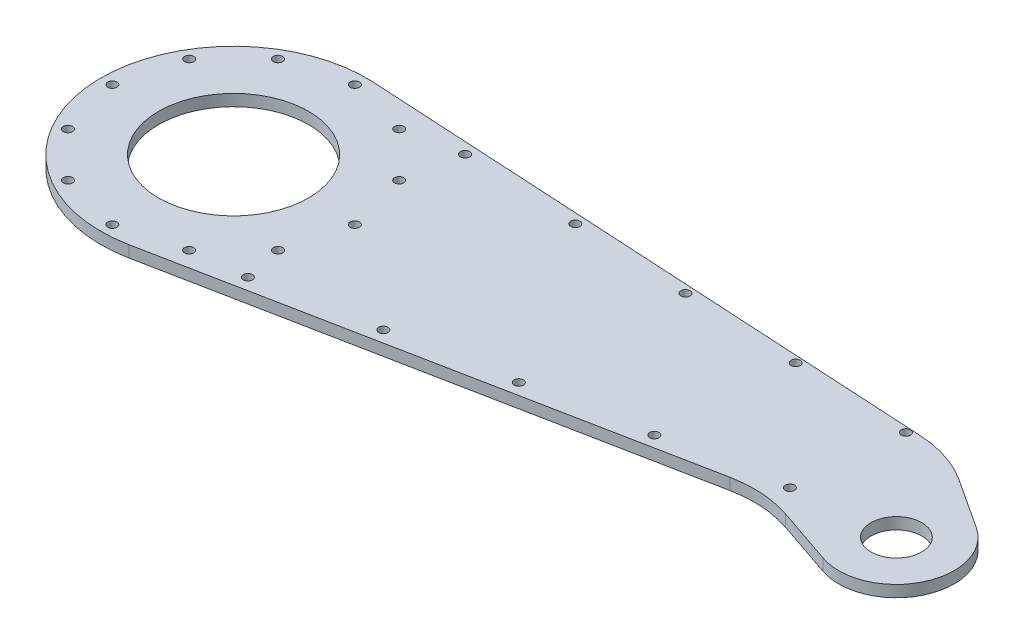
SolidWorks part; units mm, degrees
ref_plane "Front Plane" through (0, 0, 0) normal (0, 0, 1) x (1, 0, 0)
ref_plane "Top Plane" through (0, 0, 0) normal (0, 1, 0) x (1, 0, 0)
ref_plane "Right Plane" through (0, 0, 0) normal (1, 0, 0) x (0, 0, -1)
sketch "Sketch1" plane through (0, 0, 0) normal (0, 1, 0) x (1, 0, 0)
  line L0 (0, 0) -> (287, 0) construction
  line L1 (0, 0) -> (0, 57.5) construction
  line L2 (3.2274, 57.4094) -> (11.1373, -56.4111) construction
  line L3 (300.6955, 20.9149) -> (278.9303, -23.6618) construction
  line L4 (287, 0) -> (287, 25) construction
  line L5 (3.2274, 57.4094) -> (458.1164, 31.8368)
  line L6 (458.1164, 31.8368) -> (11.1373, -56.4111)
  line L7 (278.9303, -23.6618) -> (241.5626, -10.9178)
  line L8 (300.6955, 20.9149) -> (267.6658, 42.5434)
  line L9 (267.6658, 42.5434) -> (241.5626, -10.9178) construction
  circle A0 centre (0, 0) radius 57.5
  circle A1 centre (287, 0) radius 11
  circle A2 centre (287, 0) radius 25
  circle A3 centre (0, 0) radius 32.5
  point P11 (324.3481, 5.4267)
  point P14 (391.7817, 60.0218)
  point P17 (512.95, 79.9054)
  point P18 (396.0474, 59.9685)
  point P19 (440.5469, 59.7317)
  point P21 (469.5244, 67.8246)
  point P22 (0, 0)
  point P23 (0, 0)
  point P24 (469.3718, 74.4476)
  point P25 (453.8505, 70.0081)
  point P26 (0, 0)
  point P27 (0, 0)
  point P28 (476.4257, 108.7406)
  point P29 (468.6254, 114.0413)
  point P30 (477.4199, 42.3694)
  point P31 (478.4702, 36.0085)
  point P32 (478.6061, 35.0988)
  dimension "D2" = 115
  dimension "D3" = 22
  dimension "D4" = 50
  dimension "D7" = 65
  dimension "D1" = 287
  dimension "D5" = 150
  dimension "D6" = 150
extrude "Boss-Extrude2" add sketch "Sketch1" along normal blind 5 contours A0 A3 | A2 L8 L6 | A2 L6 L7 | A0 L6 L8 L5 | A2 A1 | A2 | A1 region at (145.1666, 0, -10.3864) region at (40.6023, 0, -38.3839) region at (284.8281, 0, -11.0005) region at (258.7366, 0, 13.1653)
fillet "Fillet1" radius 50 2 edges at (241.5626, 2.5, 10.9178) (267.6658, 2.5, -42.5434)
sketch "Sketch2" plane through (0, 5, 0) normal (0, 1, 0) x (1, 0, 0)
  line L0 (0, 52.5) -> (256.0779, 41.0911) construction
  line L1 (0, -52.5) -> (238.9466, -5.3243) construction
  line L2 (228.4189, -13.5128) -> (11.1373, -56.4111) construction
  line L5 (0, 52.5) -> (49.9505, 50.2746) construction
  line L6 (0, -52.5) -> (49.0687, -42.8945) construction
  circle A0 centre (0, 0) radius 52.5 construction
  circle A1 centre (0, 52.5) radius 2
  circle A2 centre (26.25, 45.4663) radius 2
  circle A3 centre (45.4663, 26.25) radius 2
  circle A4 centre (52.5, 0) radius 2
  circle A5 centre (45.4663, -26.25) radius 2
  circle A6 centre (26.25, -45.4663) radius 2
  circle A7 centre (0, -52.5) radius 2
  circle A8 centre (-26.25, -45.4663) radius 2
  circle A9 centre (-45.4663, -26.25) radius 2
  circle A10 centre (-52.5, 0) radius 2
  circle A11 centre (-45.4663, 26.25) radius 2
  circle A12 centre (-26.25, 45.4663) radius 2
  circle A13 centre (49.9505, 50.2746) radius 2
  circle A14 centre (99.9009, 48.0492) radius 2
  circle A15 centre (149.8514, 45.8238) radius 2
  circle A16 centre (199.8018, 43.5984) radius 2
  circle A17 centre (249.7523, 41.373) radius 2
  circle A18 centre (49.0687, -42.8945) radius 2
  circle A19 centre (98.1373, -33.289) radius 2
  circle A20 centre (147.206, -23.6835) radius 2
  circle A21 centre (196.2747, -14.078) radius 2
  circle A22 centre (245.3433, -4.4725) radius 2
  point P29 (0, 0)
  dimension "D1" = 105
  dimension "D2" = 4
  dimension "D4" = 6
  dimension "D5" = 50
  dimension "D7" = 50
  dimension "D6" = 6
  dimension "D3" = 12
extrude "Cut-Extrude1" cut sketch "Sketch2" against normal blind 10
